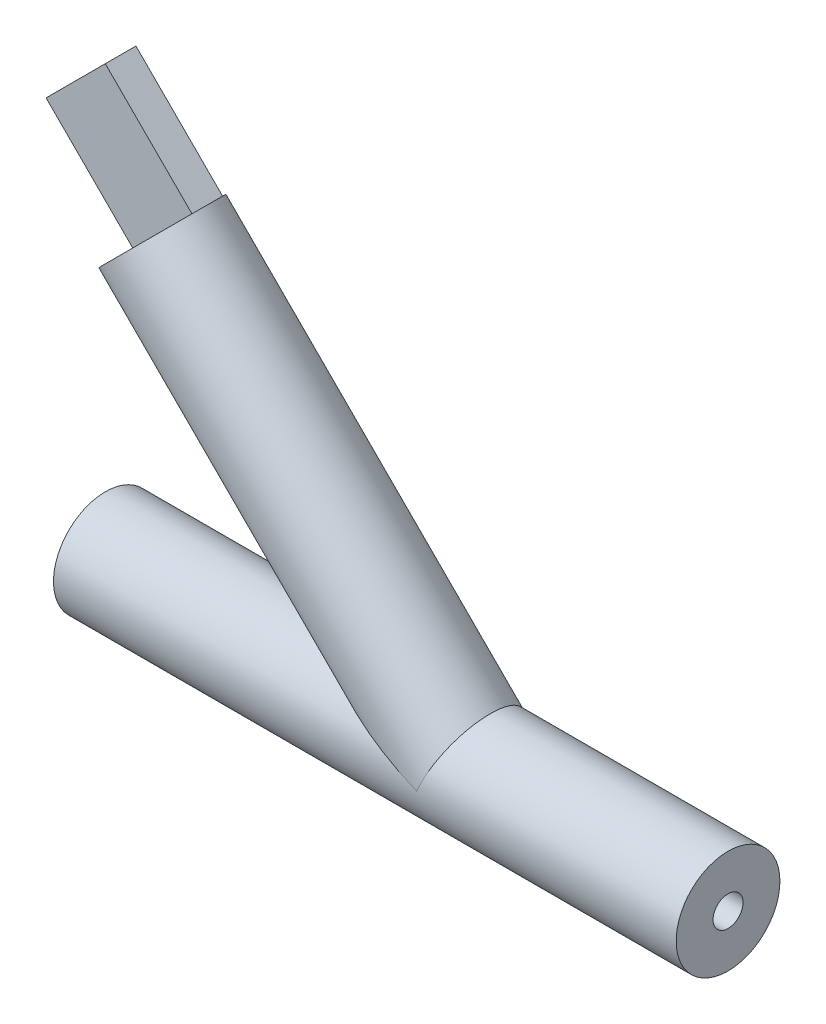
SolidWorks part; units mm, degrees
ref_plane "Front Plane" through (0, 0, 0) normal (0, 0, 1) x (1, 0, 0)
ref_plane "Top Plane" through (0, 0, 0) normal (0, 1, 0) x (1, 0, 0)
ref_plane "Right Plane" through (0, 0, 0) normal (1, 0, 0) x (0, 0, -1)
sketch "Sketch1" plane through (0, 0, 0) normal (1, 0, 0) x (0, 0, -1)
  circle A0 centre (0, 0) radius 12.7
  dimension "D1" = 25.4
extrude "Boss-Extrude1" add sketch "Sketch1" along normal blind 152.4 contours A0
sketch "Sketch4" plane through (0, 0, 0) normal (0, 1, 0) x (1, 0, 0)
  line L0 (88.9, -73.5137) -> (88.9, 26.4863)
  line L1 (152.4, -12.7) -> (152.4, 12.7) construction
  dimension "D1" = 63.5
ref_plane "Plane1" through (44.45, -44.45, 0) normal (-0.7071, 0.7071, 0) x (0.7071, 0.7071, 0)
sketch "Sketch6" plane through (0, 0, 0) normal (0, 1, 0) x (1, 0, 0)
  line L1 (152.4, -12.7) -> (152.4, 12.7) construction
  circle A0 centre (88.9, 0) radius 20
  dimension "D1" = 63.5
  dimension "D2" = 0
sketch "Sketch7" plane through (44.45, -44.45, 0) normal (-0.7071, 0.7071, 0) x (0.7071, 0.7071, 0)
  circle A0 centre (62.8618, 0) radius 12.7
  dimension "D1" = 25.4
extrude "Boss-Extrude3" add sketch "Sketch7" along normal blind 106 contours A0
sketch "Sketch10" plane through (-30.5033, 30.5033, 0) normal (-0.7071, 0.7071, 0) x (0, 0, 1)
  line L1 (-7.5, 73.1107) -> (7.5, 73.1107)
  line L2 (-7.5, 73.1107) -> (-7.5, 52.6129)
  line L3 (-7.5, 52.6129) -> (7.5, 52.6129)
  line L4 (7.5, 73.1107) -> (7.5, 52.6129)
  line L5 (-7.5, 73.1107) -> (7.5, 52.6129) construction
  line L6 (-7.5, 52.6129) -> (7.5, 73.1107) construction
  line L7 (-7.5, 73.1107) -> (0, 73.1107)
  line L8 (-7.5, 73.1107) -> (-7.5, 52.6129)
  line L9 (-7.5, 52.6129) -> (0, 52.6129)
  line L10 (0, 73.1107) -> (0, 52.6129)
  circle A0 centre (0, 62.8618) radius 12.7 construction
  point P0 (0, 62.8618)
  dimension "D1" = 15
extrude "Boss-Extrude8" add sketch "Sketch10" along normal blind 30 contours L10 L1 L2 L3 region at (13.9467, 74.9533, -3.75)
sketch "Sketch11" plane through (152.4, 0, 0) normal (1, 0, 0) x (0, 0, -1)
  circle A0 centre (0, 0) radius 3.675
  dimension "D1" = 7.35
extrude "Cut-Extrude2" cut sketch "Sketch11" against normal blind 152.4
